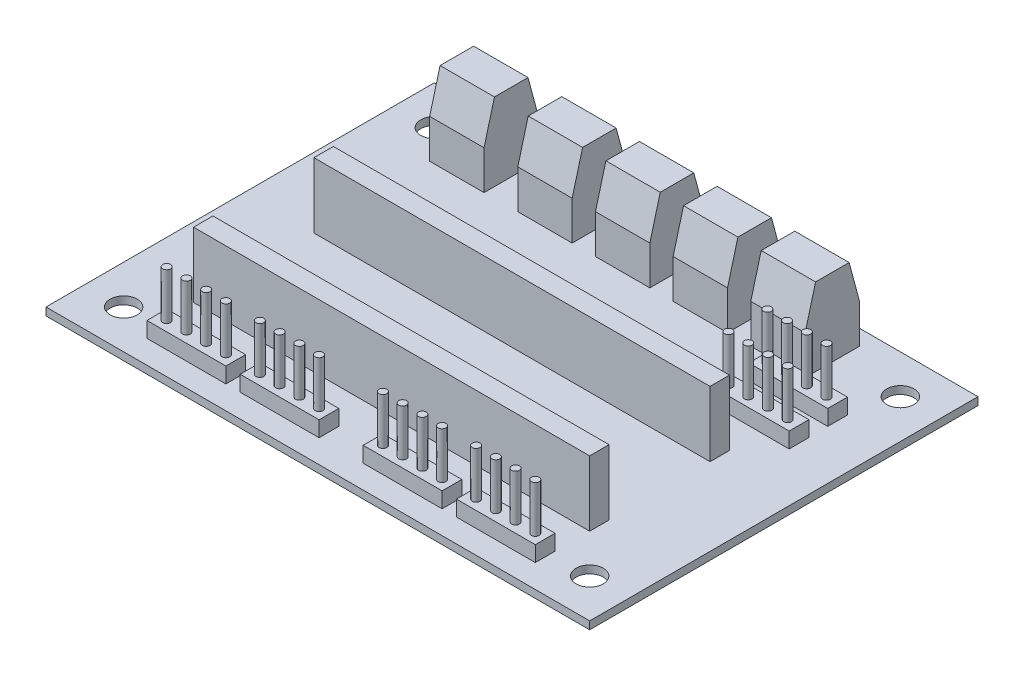
SolidWorks part; units mm, degrees
material "ABS"
ref_plane "Спереди" through (0, 0, 0) normal (0, 0, 1) x (1, 0, 0)
ref_plane "Сверху" through (0, 0, 0) normal (0, 1, 0) x (1, 0, 0)
ref_plane "Справа" through (0, 0, 0) normal (1, 0, 0) x (0, 0, -1)
sketch "Эскиз2" plane through (0, 0, 0) normal (0, 1, 0) x (1, 0, 0)
  line L0 (0, 25) -> (113.3637, 25) construction
  line L1 (0, 0) -> (70, 0)
  line L2 (0, 0) -> (0, 50)
  line L3 (0, 50) -> (70, 50)
  line L4 (70, 0) -> (70, 50)
  line L5 (35, 50) -> (35, -7.1391) construction
  circle A0 centre (5, 45) radius 1.75
  circle A1 centre (65, 45) radius 1.75
  circle A2 centre (65, 5) radius 1.75
  circle A3 centre (5, 5) radius 1.75
  dimension "D3" = 3.5
  dimension "D1" = 70
  dimension "D2" = 50
  dimension "D4" = 5
  dimension "D5" = 5
extrude "Бобышка-Вытянуть1" add sketch "Эскиз2" along normal blind 1
sketch "Эскиз3" plane through (0, 1, 0) normal (0, 1, 0) x (1, 0, 0)
  line L0 (0, 0) -> (70, 0) construction
  line L1 (9, 12.5) -> (60, 12.5)
  line L2 (9, 12.5) -> (9, 10)
  line L3 (9, 10) -> (60, 10)
  line L4 (60, 12.5) -> (60, 10)
  line L9 (70, 0) -> (70, 50) construction
  line L10 (60, 12.5) -> (60, 19) construction
  line L11 (60, 19) -> (7.0253, 19) construction
  line L12 (9, 28) -> (60, 28)
  line L13 (60, 25.5) -> (60, 28)
  line L14 (9, 25.5) -> (60, 25.5)
  line L15 (9, 25.5) -> (9, 28)
  dimension "D1" = 2.5
  dimension "D2" = 51
  dimension "D6" = 10
  dimension "D7" = 10
extrude "Бобышка-Вытянуть2" add sketch "Эскиз3" along normal blind 8.4
sketch "Эскиз4" plane through (0, 1, 0) normal (0, 1, 0) x (1, 0, 0)
  line L0 (70, 0) -> (70, 50) construction
  line L1 (60, 5.54) -> (49.84, 5.54)
  line L2 (60, 5.54) -> (60, 3)
  line L3 (60, 3) -> (49.84, 3)
  line L4 (49.84, 5.54) -> (49.84, 3)
  line L5 (0, 0) -> (70, 0) construction
  line L6 (48, 5.54) -> (48, 3)
  line L7 (35, 0) -> (35, 38.4524) construction
  line L8 (48, 5.54) -> (37.84, 5.54)
  line L9 (37.84, 5.54) -> (37.84, 3)
  line L10 (48, 3) -> (37.84, 3)
  line L11 (10, 3) -> (20.16, 3)
  line L12 (20.16, 5.54) -> (20.16, 3)
  line L13 (10, 5.54) -> (20.16, 5.54)
  line L14 (10, 5.54) -> (10, 3)
  line L15 (22, 5.54) -> (32.16, 5.54)
  line L16 (32.16, 5.54) -> (32.16, 3)
  line L17 (22, 3) -> (32.16, 3)
  line L18 (22, 5.54) -> (22, 3)
  line L19 (53.4823, 37.0132) -> (63.6423, 37.0132)
  line L20 (53.4823, 37.0132) -> (53.4823, 39.5532)
  line L21 (53.4823, 39.5532) -> (63.6423, 39.5532)
  line L22 (63.6423, 37.0132) -> (63.6423, 39.5532)
  line L23 (53.5146, 32.0132) -> (63.6746, 32.0132)
  line L24 (53.5146, 32.0132) -> (53.5146, 34.5532)
  line L25 (53.5146, 34.5532) -> (63.6746, 34.5532)
  line L26 (63.6746, 32.0132) -> (63.6746, 34.5532)
  dimension "D1" = 2.54
  dimension "D2" = 10.16
  dimension "D3" = 10
  dimension "D4" = 3
  dimension "D6" = 5
  dimension "D5" = 2
extrude "Бобышка-Вытянуть3" add sketch "Эскиз4" along normal blind 2
sketch "Эскиз5" plane through (0, 3, 0) normal (0, 1, 0) x (1, 0, 0)
  line L0 (60, 3) -> (60, 5.54) construction
  line L1 (49.84, 3) -> (60, 3) construction
  line L2 (35, 0) -> (35, 20.127) construction
  line L3 (0, 0) -> (70, 0) construction
  circle A0 centre (58.73, 4.27) radius 0.5
  circle A1 centre (56.19, 4.27) radius 0.5
  circle A2 centre (53.65, 4.27) radius 0.5
  circle A3 centre (51.11, 4.27) radius 0.5
  circle A4 centre (46.73, 4.27) radius 0.5
  circle A5 centre (44.19, 4.27) radius 0.5
  circle A6 centre (41.65, 4.27) radius 0.5
  circle A7 centre (39.11, 4.27) radius 0.5
  circle A8 centre (25.81, 4.27) radius 0.5
  circle A9 centre (11.27, 4.27) radius 0.5
  circle A10 centre (13.81, 4.27) radius 0.5
  circle A11 centre (16.35, 4.27) radius 0.5
  circle A12 centre (18.89, 4.27) radius 0.5
  circle A13 centre (23.27, 4.27) radius 0.5
  circle A14 centre (28.35, 4.27) radius 0.5
  circle A15 centre (30.89, 4.27) radius 0.5
  circle A16 centre (54.671, 33.2084) radius 0.5
  circle A17 centre (54.671, 38.2084) radius 0.5
  circle A20 centre (57.211, 33.2084) radius 0.5
  circle A21 centre (59.751, 33.2084) radius 0.5
  circle A22 centre (62.291, 33.2084) radius 0.5
  circle A23 centre (57.211, 38.2084) radius 0.5
  circle A24 centre (59.751, 38.2084) radius 0.5
  circle A25 centre (62.291, 38.2084) radius 0.5
  dimension "D1" = 1
  dimension "D2" = 1.27
  dimension "D3" = 1.27
  dimension "D4" = 4
  dimension "D5" = 2
  dimension "D6" = 4
  dimension "D7" = 2
extrude "Бобышка-Вытянуть4" add sketch "Эскиз5" along normal blind 6
sketch "Эскиз6" plane through (0, 1, 0) normal (0, 1, 0) x (1, 0, 0)
  line L0 (19.7472, 48.0002) -> (26.7472, 48.0002)
  line L5 (8.4463, 40.9536) -> (8.4463, 47.9536)
  line L6 (8.4463, 40.9536) -> (15.4463, 40.9536)
  line L7 (15.4463, 40.9536) -> (15.4463, 47.9536)
  line L8 (8.4463, 47.9536) -> (15.4463, 47.9536)
  line L9 (19.7472, 48.0002) -> (19.7472, 41.0002)
  line L10 (19.7472, 41.0002) -> (26.7472, 41.0002)
  line L11 (26.7472, 48.0002) -> (26.7472, 41.0002)
  line L12 (29.7472, 48.0002) -> (36.7472, 48.0002)
  line L13 (36.7472, 48.0002) -> (36.7472, 41.0002)
  line L14 (29.7472, 41.0002) -> (36.7472, 41.0002)
  line L15 (29.7472, 48.0002) -> (29.7472, 41.0002)
  line L16 (39.7472, 48.0002) -> (46.7472, 48.0002)
  line L17 (46.7472, 48.0002) -> (46.7472, 41.0002)
  line L18 (39.7472, 41.0002) -> (46.7472, 41.0002)
  line L19 (39.7472, 48.0002) -> (39.7472, 41.0002)
  line L20 (49.7472, 48.0002) -> (56.7472, 48.0002)
  line L21 (56.7472, 48.0002) -> (56.7472, 41.0002)
  line L22 (49.7472, 41.0002) -> (56.7472, 41.0002)
  line L23 (49.7472, 48.0002) -> (49.7472, 41.0002)
  dimension "D1" = 7
  dimension "D2" = 7
  dimension "D3" = 4
extrude "Бобышка-Вытянуть5" add sketch "Эскиз6" along normal blind 10
chamfer "Фаска1" distance 5 angle 15 10 edges at (53.2472, 11, -48.0002) (53.2472, 11, -41.0002) (43.2472, 11, -48.0002) (43.2472, 11, -41.0002) (33.2472, 11, -41.0002) (33.2472, 11, -48.0002) (23.2472, 11, -48.0002) (23.2472, 11, -41.0002) (11.9463, 11, -47.9536) (11.9463, 11, -40.9536) first distance on face at (53.2472, 6, -48.0002) first distance on face at (53.2472, 6, -41.0002) first distance on face at (43.2472, 6, -48.0002) first distance on face at (43.2472, 6, -41.0002) first distance on face at (33.2472, 6, -41.0002) first distance on face at (33.2472, 6, -48.0002) first distance on face at (23.2472, 6, -48.0002) first distance on face at (23.2472, 6, -41.0002) first distance on face at (11.9463, 6, -47.9536) first distance on face at (11.9463, 6, -40.9536)
sketch "Эскиз7" plane through (0, 0, -47.9536) normal (0, 0, -1) x (-1, 0, 0)
  circle A0 centre (-10.2599, 3.2184) radius 1
  circle A1 centre (-13.2812, 3.2184) radius 1
  circle A2 centre (-21.7063, 3.2233) radius 1
  circle A3 centre (-24.7277, 3.2233) radius 1
  circle A4 centre (-34.7277, 3.2233) radius 1
  circle A5 centre (-31.7063, 3.2233) radius 1
  circle A6 centre (-44.7277, 3.2233) radius 1
  circle A7 centre (-41.7063, 3.2233) radius 1
  circle A8 centre (-54.7277, 3.2233) radius 1
  circle A9 centre (-51.7063, 3.2233) radius 1
  dimension "D1" = 4
extrude "Вырез-Вытянуть1" cut sketch "Эскиз7" against normal blind 2 from surface starting at face at (33.2472, 3.5, -48.0002)
